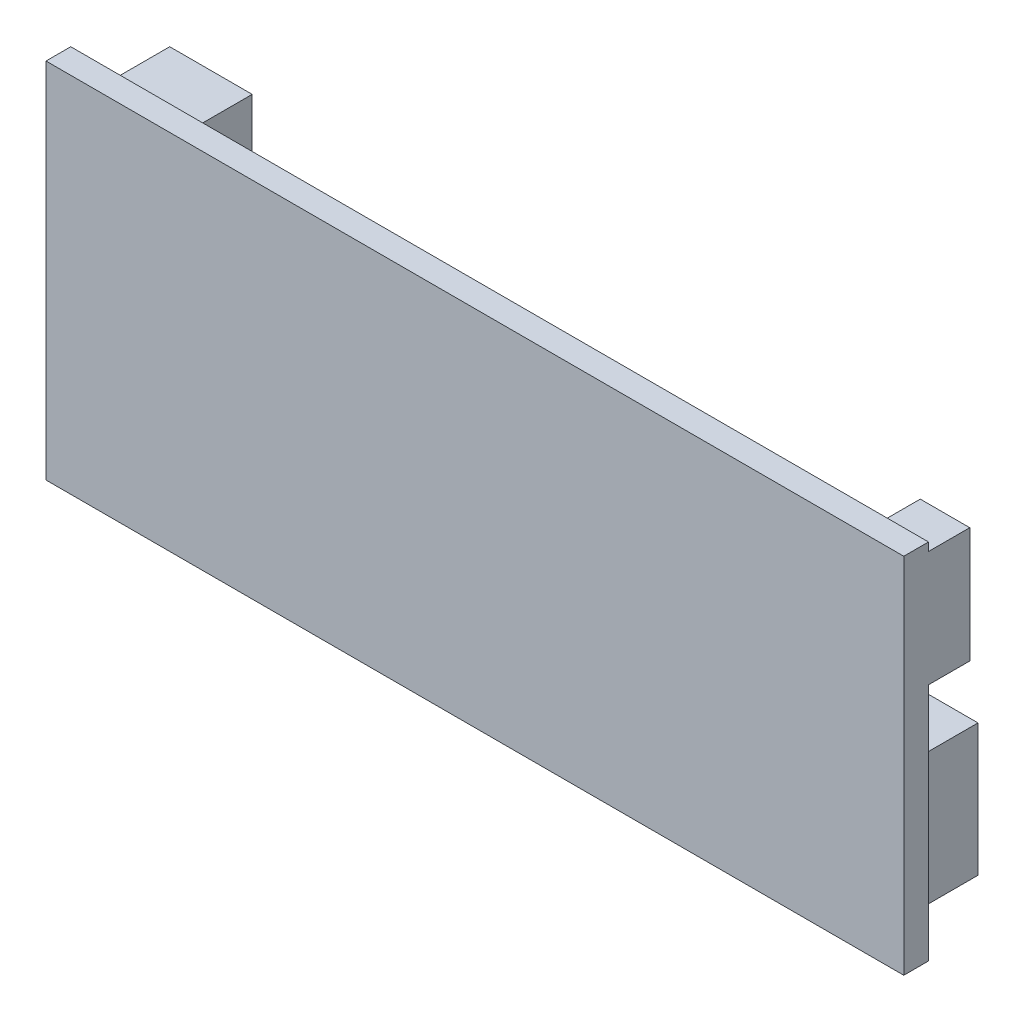
SolidWorks part; units mm, degrees
ref_plane "Front Plane" through (0, 0, 0) normal (0, 0, 1) x (1, 0, 0)
ref_plane "Top Plane" through (0, 0, 0) normal (0, 1, 0) x (1, 0, 0)
ref_plane "Right Plane" through (0, 0, 0) normal (1, 0, 0) x (0, 0, -1)
sketch "Sketch1" plane through (0, 0, 0) normal (0, 0, 1) x (1, 0, 0)
  line L0 (-19.2815, 22) -> (-19.2815, 0)
  line L1 (-19.2815, 0) -> (32.7185, 0)
  line L2 (32.7185, 0) -> (32.7185, 22)
  line L3 (32.7185, 22) -> (-19.2815, 22)
extrude "Boss-Extrude1" add sketch "Sketch1" along normal blind 1.5
sketch "Sketch2" plane through (0, 0, 0) normal (0, 0, -1) x (-1, 0, 0)
  line L0 (-32.7185, 0) -> (-32.7185, 22) construction
  line L1 (17.7815, 20.5) -> (12.7815, 20.5)
  line L2 (17.7815, 20.5) -> (17.7815, 15.5)
  line L3 (17.7815, 15.5) -> (12.7815, 15.5)
  line L4 (12.7815, 20.5) -> (12.7815, 15.5)
  line L5 (-31.2185, 1.5) -> (-21.2185, 1.5)
  line L6 (-31.2185, 1.5) -> (-31.2185, 9.5)
  line L7 (-31.2185, 9.5) -> (-21.2185, 9.5)
  line L8 (-21.2185, 1.5) -> (-21.2185, 9.5)
  line L9 (-32.7185, 21.5) -> (-29.7185, 21.5)
  line L10 (-32.7185, 21.5) -> (-32.7185, 14.5)
  line L11 (-32.7185, 14.5) -> (-29.7185, 14.5)
  line L12 (-29.7185, 21.5) -> (-29.7185, 14.5)
  line L13 (-28.7185, 21.5) -> (-32.7185, 21.5) construction
  line L14 (-28.7185, 14.5) -> (-32.7185, 14.5) construction
  line L15 (19.2815, 22) -> (19.2815, 0) construction
  line L16 (17.7815, 7.9) -> (19.2815, 7.9)
  line L17 (17.7815, 7.9) -> (17.7815, 3.0979)
  line L18 (17.7815, 3.0979) -> (19.2815, 3.0979)
  line L19 (19.2815, 7.9) -> (19.2815, 3.0979)
  line L20 (32.1478, 3.0979) -> (17.1478, 3.0979) construction
  dimension "D1" = 5
  dimension "D2" = 5
  dimension "D3" = 10
  dimension "D4" = 8
  dimension "D5" = 3
extrude "Boss-Extrude2" add sketch "Sketch2" along normal blind 2.5
sketch "Sketch3" plane through (0, 0, -2.5) normal (0, 0, -1) x (-1, 0, 0)
  line L0 (-31.2185, 9.5) -> (-31.2185, 1.5) construction
  line L1 (-31.2185, 1.5) -> (-21.2185, 1.5) construction
  line L2 (-21.2185, 1.5) -> (-21.2185, 9.5) construction
  line L3 (-21.2185, 9.5) -> (-31.2185, 9.5) construction
  line L4 (17.7815, 7.9) -> (17.7815, 3.0979) construction
  line L5 (17.7815, 3.0979) -> (19.2815, 3.0979) construction
  line L6 (19.2815, 3.0979) -> (19.2815, 7.9) construction
  line L7 (19.2815, 7.9) -> (17.7815, 7.9) construction
  line L8 (17.7815, 15.5) -> (17.7815, 20.5) construction
  line L9 (17.7815, 20.5) -> (12.7815, 20.5) construction
  line L10 (12.7815, 20.5) -> (12.7815, 15.5) construction
  line L11 (12.7815, 15.5) -> (17.7815, 15.5) construction
  line L12 (-31.2185, 9.5) -> (-31.2185, 1.5)
  line L13 (-31.2185, 1.5) -> (-21.2185, 1.5)
  line L14 (-21.2185, 1.5) -> (-21.2185, 9.5)
  line L15 (-21.2185, 9.5) -> (-31.2185, 9.5)
  line L16 (17.7815, 7.9) -> (17.7815, 3.0979)
  line L17 (17.7815, 3.0979) -> (19.2815, 3.0979)
  line L18 (19.2815, 3.0979) -> (19.2815, 7.9)
  line L19 (19.2815, 7.9) -> (17.7815, 7.9)
  line L20 (17.7815, 15.5) -> (17.7815, 20.5)
  line L21 (17.7815, 20.5) -> (12.7815, 20.5)
  line L22 (12.7815, 20.5) -> (12.7815, 15.5)
  line L23 (12.7815, 15.5) -> (17.7815, 15.5)
extrude "Boss-Extrude3" add sketch "Sketch3" along normal blind 2
